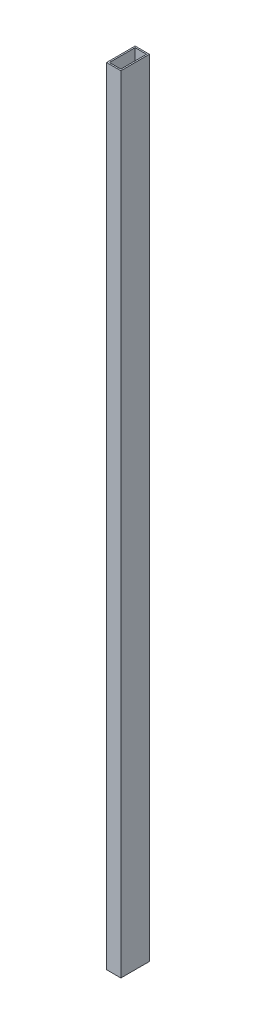
SolidWorks part; units mm, degrees
ref_plane "Спереди" through (0, 0, 0) normal (0, 0, 1) x (1, 0, 0)
ref_plane "Сверху" through (0, 0, 0) normal (0, 1, 0) x (1, 0, 0)
ref_plane "Справа" through (0, 0, 0) normal (1, 0, 0) x (0, 0, -1)
sketch "Эскиз1" plane through (0, 0, 0) normal (0, 1, 0) x (1, 0, 0)
  line L1 (-10, 20) -> (10, 20)
  line L2 (-10, 20) -> (-10, -20)
  line L3 (-10, -20) -> (10, -20)
  line L4 (10, 20) -> (10, -20)
  line L5 (-10, 20) -> (10, -20) construction
  line L6 (-10, -20) -> (10, 20) construction
  point P0 (0, 0)
extrude "Вытянуть-Тонкостенный1" add sketch "Эскиз1" along normal blind 1100 thin thin type one direction reverse wall 2
